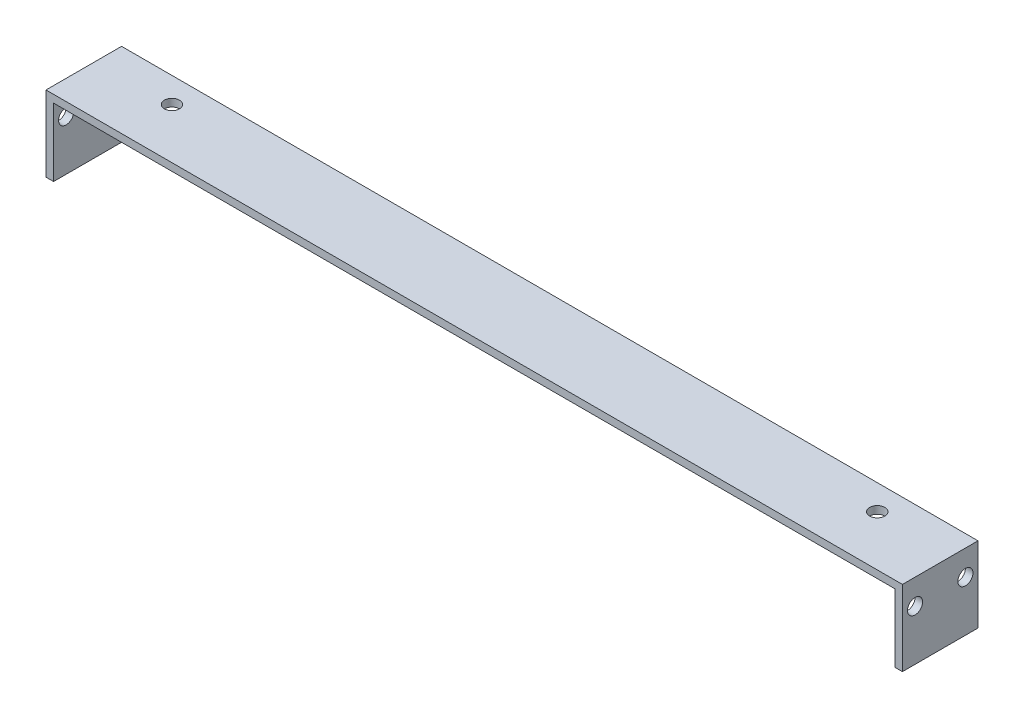
SolidWorks part; units mm, degrees
ref_plane "Front Plane" through (0, 0, 0) normal (0, 0, 1) x (1, 0, 0)
ref_plane "Top Plane" through (0, 0, 0) normal (0, 1, 0) x (1, 0, 0)
ref_plane "Right Plane" through (0, 0, 0) normal (1, 0, 0) x (0, 0, -1)
sketch "Sketch1" plane through (0, 0, 0) normal (0, 1, 0) x (1, 0, 0)
  line L1 (0, 0) -> (167, 0)
  line L2 (0, 0) -> (0, 15)
  line L3 (0, 15) -> (167, 15)
  line L4 (167, 0) -> (167, 15)
  dimension "D1" = 15
  dimension "D2" = 167
extrude "Boss-Extrude1" add sketch "Sketch1" along normal blind 1.5
sketch "Sketch2" plane through (167, 0, 0) normal (1, 0, 0) x (0, 0, -1)
  line L1 (0, 1.5) -> (15, 1.5)
  line L2 (0, 1.5) -> (0, -13.5)
  line L3 (0, -13.5) -> (15, -13.5)
  line L4 (15, 1.5) -> (15, -13.5)
  dimension "D1" = 15
  dimension "D2" = 15
extrude "Boss-Extrude2" add sketch "Sketch2" along normal blind 1.5
sketch "Sketch3" plane through (0, 0, 0) normal (-1, 0, 0) x (0, 0, 1)
  line L1 (0, 1.5) -> (-15, 1.5)
  line L2 (0, 1.5) -> (0, -13.5)
  line L3 (0, -13.5) -> (-15, -13.5)
  line L4 (-15, 1.5) -> (-15, -13.5)
  dimension "D1" = 15
  dimension "D2" = 15
extrude "Boss-Extrude3" add sketch "Sketch3" along normal blind 1.5
sketch "Sketch4" plane through (0, 1.5, 0) normal (0, 1, 0) x (1, 0, 0)
  line L1 (-1.5, 0) -> (-1.5, 15) construction
  circle A0 centre (13.5, 10) radius 1.5
  circle A1 centre (153.5, 10) radius 1.5
  dimension "D2" = 15
sketch "Sketch5" plane through (168.5, 0, 0) normal (1, 0, 0) x (0, 0, -1)
  line L0 (15, 1.5) -> (0, 1.5) construction
  line L5 (0, 1.5) -> (0, -13.5) construction
  circle A0 centre (2.5, -3.5) radius 1.5
  circle A1 centre (12.5, -3.5) radius 1.5
  dimension "D1" = 2.5
  dimension "D2" = 5
  dimension "D3" = 5
  dimension "D4" = 10
extrude "Cut-Extrude1" cut sketch "Sketch5" against normal blind 10000 and the other way blind 1000
extrude "Cut-Extrude2" cut sketch "Sketch4" against normal blind 10000 and the other way blind 10000
